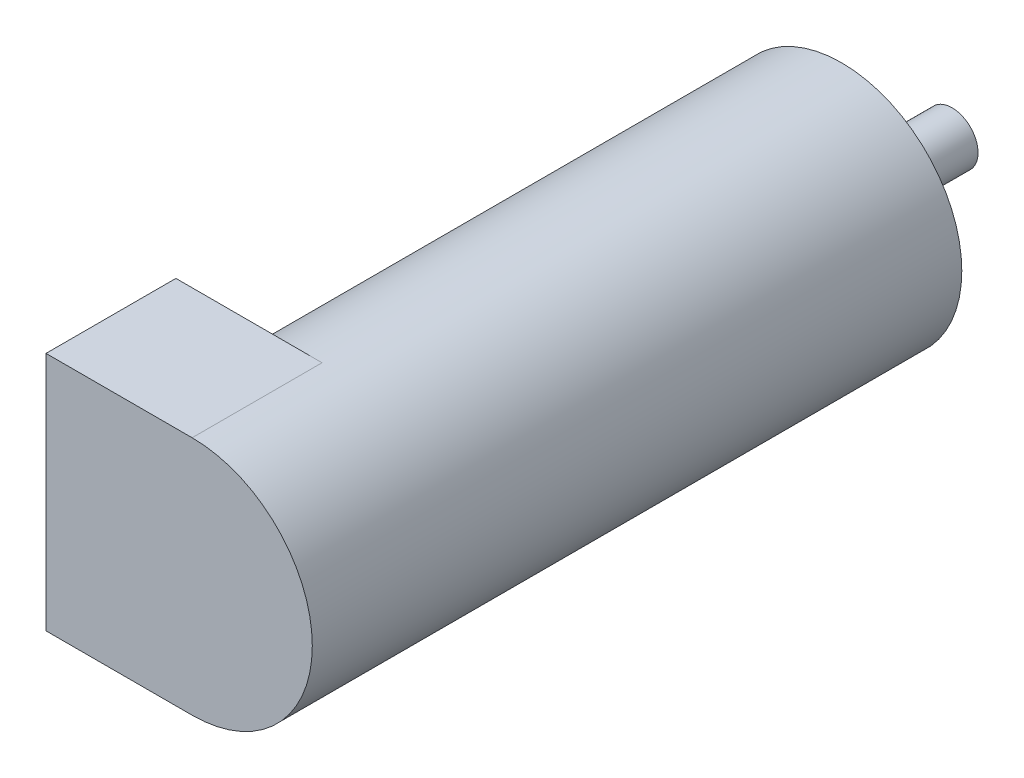
SolidWorks part; units mm, degrees
ref_plane "Спереди" through (0, 0, 0) normal (0, 0, 1) x (1, 0, 0)
ref_plane "Сверху" through (0, 0, 0) normal (0, 1, 0) x (1, 0, 0)
ref_plane "Справа" through (0, 0, 0) normal (1, 0, 0) x (0, 0, -1)
sketch "Эскиз1" plane through (0, 0, 0) normal (0, 0, 1) x (1, 0, 0)
  circle A0 centre (0, 0) radius 18.5
  dimension "D1" = 37
extrude "Бобышка-Вытянуть1" add sketch "Эскиз1" along normal blind 80
sketch "Эскиз2" plane through (0, 0, 80) normal (0, 0, 1) x (1, 0, 0)
  line L0 (0, 18.5) -> (-22.5, 18.5)
  line L1 (-22.5, 18.5) -> (-22.5, -18.5)
  line L2 (-22.5, -18.5) -> (0, -18.5)
  line L3 (18.5, 0) -> (18.5, 36.1764) construction
  circle A0 centre (0, 0) radius 18.5 construction
  arc A1 (0, -18.5) -> (0, 18.5) centre (0, 0) ccw
  dimension "D1" = 41
extrude "Бобышка-Вытянуть2" add sketch "Эскиз2" along normal blind 20
sketch "Эскиз3" plane through (0, 0, 0) normal (0, 0, -1) x (-1, 0, 0)
  circle A0 centre (0, 0) radius 4
  dimension "D1" = 8
extrude "Бобышка-Вытянуть3" add sketch "Эскиз3" along normal blind 17
sketch "Эскиз4" plane through (0, 0, 0) normal (0, 0, -1) x (-1, 0, 0)
  line L0 (0, 0) -> (0, -18.1277) construction
  line L1 (6.3408, 0) -> (24.5695, 0) construction
  circle A0 centre (15, 0) radius 1.5
  circle A1 centre (0, 15) radius 1.5
  circle A2 centre (-15, 0) radius 1.5
  circle A3 centre (0, -15) radius 1.5
  point P2 (0, 0)
  point P13 (0, 0)
  point P15 (15, 0)
  point P16 (0, 0)
  dimension "D1" = 3
  dimension "D2" = 15
  dimension "D3" = 15
extrude "Вырез-Вытянуть1" cut sketch "Эскиз4" against normal blind 3
